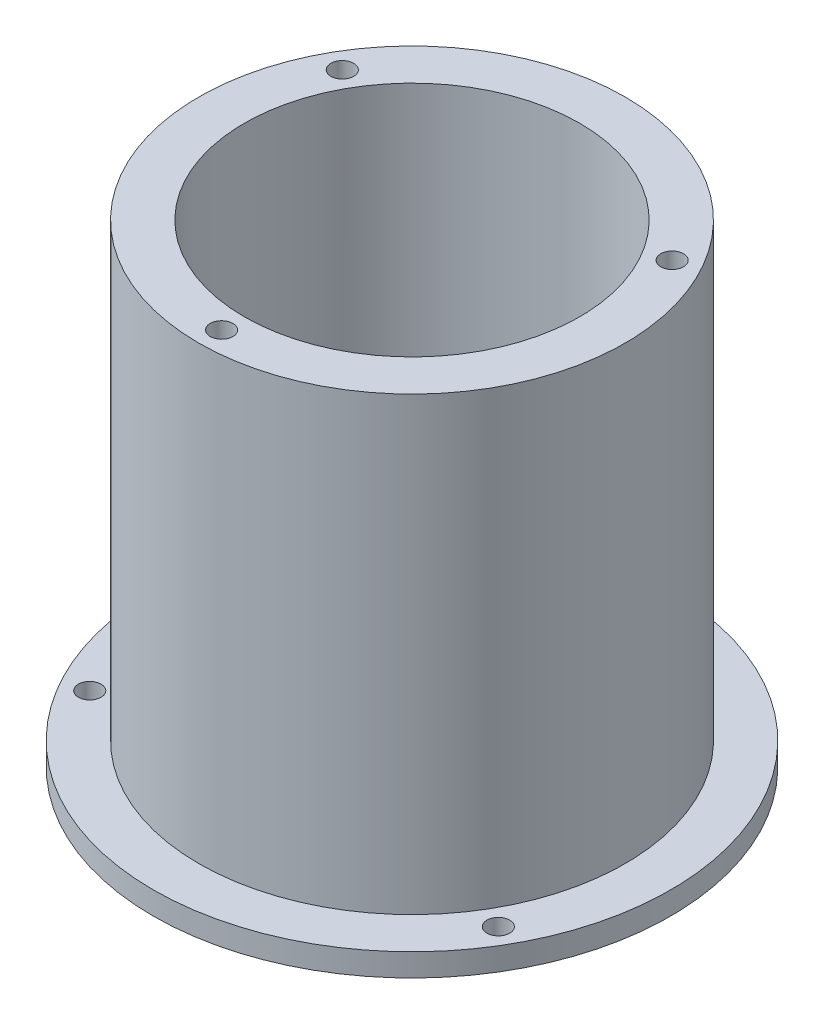
SolidWorks part; units mm, degrees
ref_plane "Front Plane" through (0, 0, 0) normal (0, 0, 1) x (1, 0, 0)
ref_plane "Top Plane" through (0, 0, 0) normal (0, 1, 0) x (1, 0, 0)
ref_plane "Right Plane" through (0, 0, 0) normal (1, 0, 0) x (0, 0, -1)
sketch "Sketch1" plane through (0, 0, 0) normal (0, 1, 0) x (1, 0, 0)
  circle A0 centre (0, 0) radius 45.5
  circle A1 centre (0, 0) radius 29.5
  dimension "D1" = 91
  dimension "D2" = 59
extrude "Boss-Extrude1" add sketch "Sketch1" along normal blind 4
sketch "Sketch2" plane through (0, 4, 0) normal (0, 1, 0) x (1, 0, 0)
  circle A0 centre (0, 0) radius 37.5
  circle A1 centre (0, 0) radius 29.5
extrude "Boss-Extrude2" add sketch "Sketch2" along normal blind 79.3
sketch "Sketch4" plane through (0, 4, 0) normal (0, 1, 0) x (1, 0, 0)
  circle A0 centre (0, 41.5) radius 2
  dimension "D1" = 4
  dimension "D2" = 41.5
extrude "Cut-Extrude1" cut sketch "Sketch4" against normal blind 83.3
pattern_circular "CirPattern1" count 3 over 360 about axis through (0, 4, 0) along (0, 1, 0) of "Cut-Extrude1"
sketch "Sketch6" plane through (0, 83.3, 0) normal (0, 1, 0) x (1, 0, 0)
  line L0 (0, 0) -> (0, 37.5) construction
  circle A0 centre (-29.0119, 16.75) radius 2
  circle A2 centre (0, 0) radius 37.5 construction
  dimension "D1" = 4
  dimension "D3" = 60
  dimension "D2" = 33.5
extrude "Cut-Extrude2" cut sketch "Sketch6" against normal blind 6
pattern_circular "CirPattern2" count 3 over 360 about axis through (0, 83.3, 0) along (0, 1, 0) of "Cut-Extrude2"
sketch "Sketch8" plane through (0, 0, 0) normal (0, -1, 0) x (1, 0, 0)
  circle A0 centre (0, 0) radius 30.5
  dimension "D1" = 61
extrude "Cut-Extrude4" cut sketch "Sketch8" against normal blind 6
